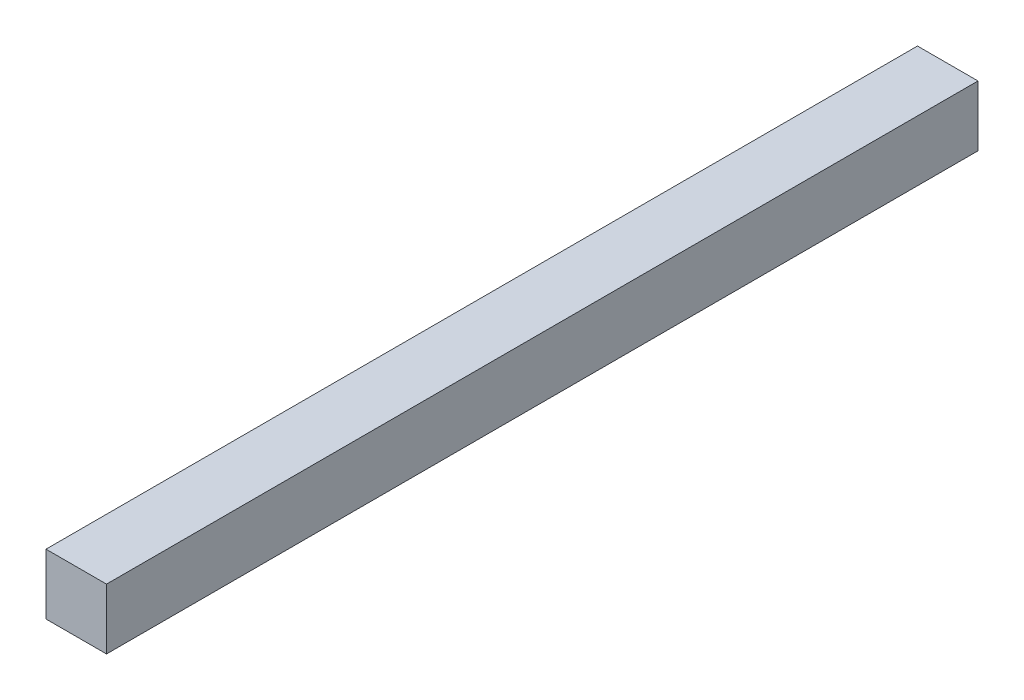
SolidWorks part; units mm, degrees
ref_plane "前视基准面" through (0, 0, 0) normal (0, 0, 1) x (1, 0, 0)
ref_plane "上视基准面" through (0, 0, 0) normal (0, 1, 0) x (1, 0, 0)
ref_plane "右视基准面" through (0, 0, 0) normal (1, 0, 0) x (0, 0, -1)
other "Configuration Table"
sketch "Sketch1" plane through (0, 0, 0) normal (0, 0, 1) x (1, 0, 0)
  line L1 (-25, -25) -> (25, -25)
  line L2 (-25, -25) -> (-25, 25)
  line L3 (-25, 25) -> (25, 25)
  line L4 (25, -25) -> (25, 25)
  line L5 (-25, -25) -> (25, 25) construction
  line L6 (-25, 25) -> (25, -25) construction
  point P0 (0, 0)
extrude "Boss-Extrude1" add sketch "Sketch1" along normal blind 720
sketch "Sketch2" plane through (0, 0, 0) normal (0, 0, 1) x (1, 0, 0)
  circle A0 centre (0, 0) radius 2.5
ref_plane "top_face" through (0, 0, 720) normal (0, 0, 1) x (1, 0, 0)
ref_plane "bottom_face" through (0, 0, 0) normal (0, 0, 1) x (1, 0, 0)
sketch3d "3DSketch1"
  line L0 (0, 0, 705) -> (0, 0, 720) construction
ref_axis "mount_axis" through (0, 0, 705) along (0, 0, 1)
